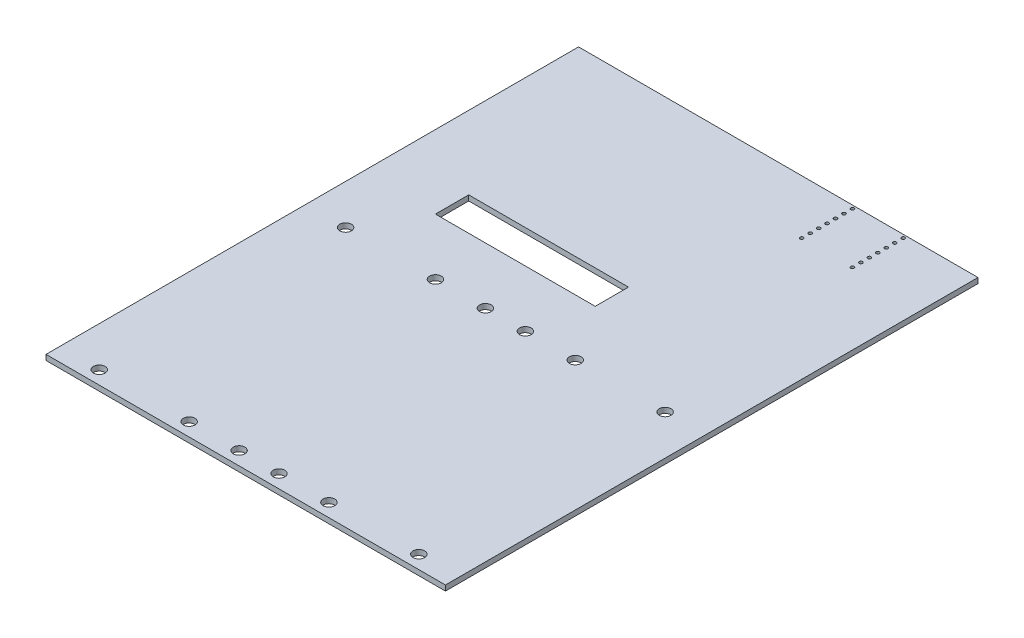
SolidWorks part; units mm, degrees
ref_plane "Front Plane" through (0, 0, 0) normal (0, 0, 1) x (1, 0, 0)
ref_plane "Top Plane" through (0, 0, 0) normal (0, 1, 0) x (1, 0, 0)
ref_plane "Right Plane" through (0, 0, 0) normal (1, 0, 0) x (0, 0, -1)
sketch "Sketch1" plane through (0, 0, 0) normal (0, 1, 0) x (1, 0, 0)
  line L1 (0, 0) -> (120, 0)
  line L2 (0, 0) -> (0, -160)
  line L3 (0, -160) -> (120, -160)
  line L4 (120, 0) -> (120, -160)
  line L11 (95.3275, 1.75) -> (95.3275, 2.77)
  line L12 (8, -78) -> (58, -78)
  line L13 (8, -78) -> (8, -160)
  line L14 (8, -160) -> (58, -160)
  line L15 (58, -78) -> (58, -160)
  line L16 (62, -78) -> (112, -78)
  line L17 (62, -78) -> (62, -160)
  line L18 (62, -160) -> (112, -160)
  line L19 (112, -78) -> (112, -160)
  line L24 (70, -65) -> (22, -65)
  line L25 (70, -65) -> (70, -55)
  line L26 (18.43, -160) -> (18.43, -166.096)
  line L27 (18.43, -166.096) -> (48.43, -166.096)
  line L28 (48.43, -166.096) -> (48.43, -160)
  line L43 (60, -78) -> (60, -160) construction
  line L44 (101.57, -160) -> (101.57, -166.096)
  line L45 (101.57, -166.096) -> (71.57, -166.096)
  line L46 (71.57, -166.096) -> (71.57, -160)
  line L54 (70, -55) -> (22, -55)
  line L55 (22, -65) -> (22, -55)
  line L56 (85, -160) -> (35, -160)
  line L57 (85, -160) -> (85, -78)
  line L58 (85, -78) -> (35, -78)
  line L59 (35, -160) -> (35, -78)
  line L68 (99.7675, -19.08) -> (81.9875, -19.08)
  line L69 (99.7675, -19.08) -> (99.7675, 1.75)
  line L70 (99.7675, 1.75) -> (81.9875, 1.75)
  line L71 (81.9875, -19.08) -> (81.9875, 1.75)
  line L72 (95.3275, 2.77) -> (86.4375, 2.77)
  line L73 (86.4375, 2.77) -> (86.4375, 1.75)
  circle A4 centre (12, -82) radius 1.75
  circle A5 centre (54, -82) radius 1.75
  circle A6 centre (12, -156) radius 1.75
  circle A7 centre (54, -156) radius 1.75
  circle A8 centre (66, -82) radius 1.75
  circle A9 centre (108, -82) radius 1.75
  circle A10 centre (66, -156) radius 1.75
  circle A11 centre (108, -156) radius 1.75
  circle A80 centre (81, -156) radius 1.75
  circle A81 centre (39, -156) radius 1.75
  circle A82 centre (39, -82) radius 1.75
  circle A83 centre (81, -82) radius 1.75
  circle A98 centre (83.2575, -0.98) radius 0.5
  circle A99 centre (98.4975, -0.98) radius 0.5
  circle A100 centre (98.4975, -3.52) radius 0.5
  circle A101 centre (98.4975, -6.06) radius 0.5
  circle A102 centre (98.4975, -8.6) radius 0.5
  circle A103 centre (98.4975, -11.14) radius 0.5
  circle A104 centre (98.4975, -13.68) radius 0.5
  circle A105 centre (98.4975, -16.22) radius 0.5
  circle A106 centre (83.2575, -3.52) radius 0.5
  circle A107 centre (83.2575, -6.06) radius 0.5
  circle A108 centre (83.2575, -8.6) radius 0.5
  circle A109 centre (83.2575, -11.14) radius 0.5
  circle A110 centre (83.2575, -13.68) radius 0.5
  circle A111 centre (83.2575, -16.22) radius 0.5
  point P93 (0, 0)
  dimension "D11" = 3.5
  dimension "D27" = 3.5
  dimension "D46" = 1
  dimension "D1" = 120
  dimension "D2" = 160
  dimension "D3" = 42
  dimension "D4" = 42
  dimension "D5" = 74
  dimension "D6" = 12
  dimension "D7" = 12
  dimension "D19" = 82
  dimension "D20" = 50
  dimension "D21" = 4
  dimension "D22" = 4
  dimension "D23" = 4
  dimension "D24" = 4
  dimension "D30" = 30
  dimension "D31" = 6.096
  dimension "D32" = 9.57
  dimension "D37" = 2
  dimension "D15" = 10
  dimension "D17" = 48
  dimension "D25" = 50
  dimension "D26" = 35
  dimension "D28" = 4
  dimension "D29" = 4
  dimension "D16" = 95
  dimension "D18" = 50
  dimension "D42" = 17.78
  dimension "D43" = 20.83
  dimension "D44" = 1.02
  dimension "D45" = 8.89
  dimension "D50" = 4.45
  dimension "D47" = 2.73
  dimension "D48" = 1.27
  dimension "D8" = 1.75
  dimension "D9" = 20.2325
  dimension "D10" = 2.54
  dimension "D12" = 1.27
  dimension "D49" = 2
  dimension "D51" = 7
extrude "Boss-Extrude2" add sketch "Sketch1" along normal blind 1.6 contours L68 L71 L1 L2 L3 L13 L12 L58 L16 L19 L4 L69 L24 L55 L54 L25 | L71 L68 L69 L1 A111 A110 A109 A108 A107 A106 A105 A104 A103 A102 A101 A100 A99 A98 | L18 L57 L16 L17 L3 A83 A80 A10 A8 | L59 L3 L15 L12 A82 A81 A7 A5 | L14 L59 L12 L13 L3 A6 A4 | L57 L3 L18 L19 L16 A11 A9 | L43 L58 L15 L3 | L58 L43 L56 L17 region at (59.6189, 0, 49.6441) region at (90.8775, 0, 9.5715) region at (21.5833, 0, 119) region at (46.5, 0, 119) region at (98.4167, 0, 119) region at (59, 0, 119) region at (61, 0, 119) region at (73.5, 0, 119)
equation "\"D4@Sketch1\"=\"D3@Sketch1\""
equation "\"D24@Sketch1\"=\"D22@Sketch1\""
equation "\"D23@Sketch1\"=\"D22@Sketch1\""
equation "\"D25@Sketch1\"=\"D20@Sketch1\""
equation "\"D26@Sketch1\"=(\"D1@Sketch1\"-\"D25@Sketch1\")/2"
equation "\"D27@Sketch1\"=\"D11@Sketch1\""
equation "\"D28@Sketch1\"=\"D24@Sketch1\""
equation "\"D29@Sketch1\"=\"D22@Sketch1\""
